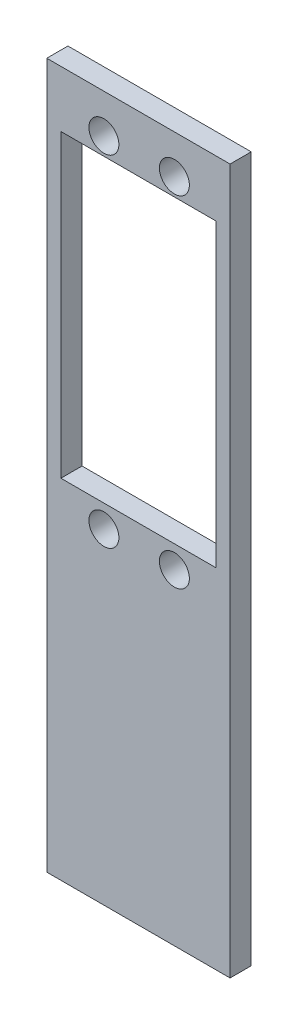
SolidWorks part; units mm, degrees
ref_plane "Front Plane" through (0, 0, 0) normal (0, 0, 1) x (1, 0, 0)
ref_plane "Top Plane" through (0, 0, 0) normal (0, 1, 0) x (1, 0, 0)
ref_plane "Right Plane" through (0, 0, 0) normal (1, 0, 0) x (0, 0, -1)
sketch "Sketch1" plane through (0, 0, 7.303) normal (0, 0, -1) x (-1, 0, 0)
  line L1 (1.3253, -21.2507) -> (27.3253, -21.2507)
  line L2 (1.3253, -21.2507) -> (1.3253, 78.7493)
  line L3 (1.3253, 78.7493) -> (27.3253, 78.7493)
  line L4 (27.3253, -21.2507) -> (27.3253, 78.7493)
  dimension "D1" = 100
  dimension "D2" = 26
extrude "Boss-Extrude1" add sketch "Sketch1" along normal blind 3
sketch "Sketch2" plane through (0, 0, 4.303) normal (0, 0, -1) x (-1, 0, 0)
  line L0 (27.3253, -21.2507) -> (27.3253, 78.7493) construction
  line L1 (25.3253, 70.7493) -> (3.3253, 70.7493)
  line L2 (25.3253, 70.7493) -> (25.3253, 28.1493)
  line L3 (25.3253, 28.1493) -> (3.3253, 28.1493)
  line L4 (3.3253, 70.7493) -> (3.3253, 28.1493)
  line L5 (27.3253, 78.7493) -> (1.3253, 78.7493) construction
  dimension "D1" = 22
  dimension "D2" = 42.6
  dimension "D3" = 2
  dimension "D4" = 8
extrude "Cut-Extrude1" cut sketch "Sketch2" against normal blind 3
hole_wizard "Hole1" positions "Sketch3" profile "Sketch4" legacy end condition through all
sketch "Sketch3" plane through (0, 0, 7.303) normal (0, 0, 1) x (1, 0, 0)
  point P0 (-19.2253, 73.2493)
  point P4 (-9.2253, 73.2493)
  point P7 (-19.2253, 24.9493)
  point P10 (-9.2253, 24.9493)
sketch "Sketch4" plane through (-19.2253, 73.2493, 7.303) normal (1, 0, 0) x (0, -1, 0)
  line L0 (0, 0) -> (0, 3)
  line L1 (0, 3) -> (2.125, 3)
  line L2 (2.125, 3) -> (2.125, 0)
  line L3 (2.125, 0) -> (0, 0)
  line L4 (0, 110) -> (0, -10) construction
  dimension "Diameter" = 4.25
  dimension "Depth" = 3
